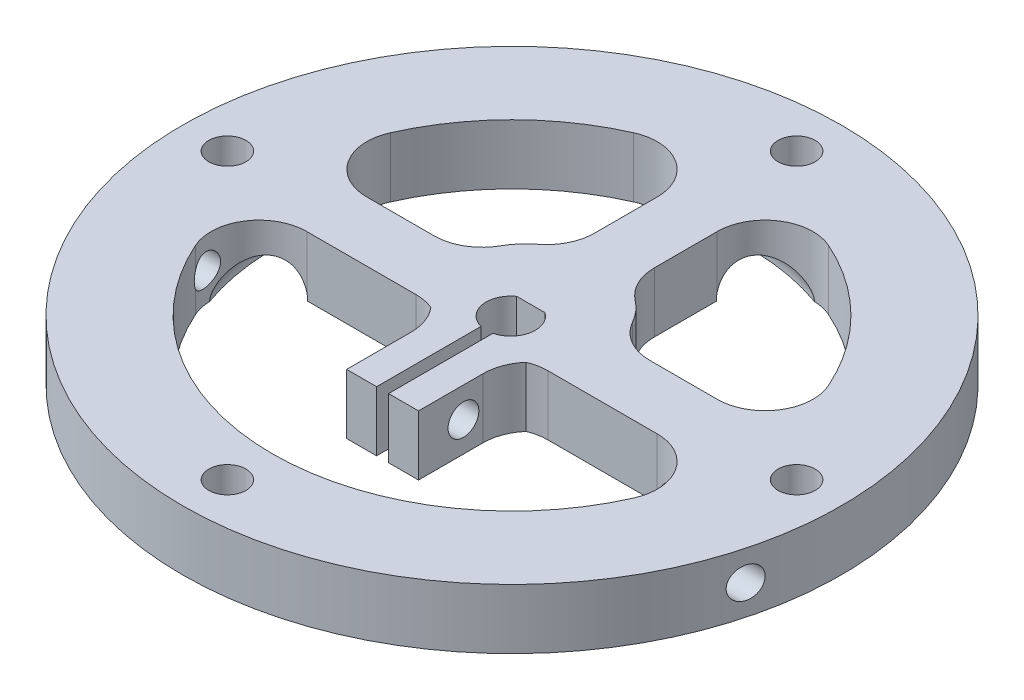
SolidWorks part; units mm, degrees
ref_plane "Front Plane" through (0, 0, 0) normal (0, 0, 1) x (1, 0, 0)
ref_plane "Top Plane" through (0, 0, 0) normal (0, 1, 0) x (1, 0, 0)
ref_plane "Right Plane" through (0, 0, 0) normal (1, 0, 0) x (0, 0, -1)
ref_plane "Plane1" through (0, 46.35, 0) normal (0, 1, 0) x (1, 0, 0)
sketch "Sketch1" plane through (0, 46.35, 0) normal (0, 1, 0) x (1, 0, 0)
  line L0 (-3.81, -4.191) -> (-3.81, -13.716)
  line L3 (-1.5, 2) -> (1.5, 2) construction
  line L4 (-1.5, 2) -> (1.5, 2)
  line L5 (0, -0.127) -> (0, -30.1625) construction
  line L6 (3.81, -8.9535) -> (-3.81, -8.9535) construction
  line L7 (-3.81, -13.716) -> (-0.635, -13.716)
  line L8 (-0.635, -13.716) -> (-0.635, -2.6511)
  line L10 (3.81, -13.716) -> (0.635, -13.716)
  line L11 (0.635, -13.716) -> (0.635, -2.6511)
  line L12 (3.81, -13.716) -> (3.81, -4.191)
  line L13 (0, 0) -> (0, 30.1625) construction
  line L14 (0, 0) -> (-30.1625, 0) construction
  line L15 (0, 0) -> (30.1625, 0) construction
  line L16 (-3.175, 8.9803) -> (-3.175, 25.2008)
  line L17 (3.175, 8.9803) -> (3.175, 25.2008)
  line L18 (-7.8651, 3.175) -> (-25.2008, 3.175)
  line L19 (-5.3988, -3.175) -> (-25.2008, -3.175)
  line L20 (5.3988, -3.175) -> (25.2008, -3.175)
  line L21 (7.8651, 3.175) -> (25.2008, 3.175)
  arc A0 (-3.81, -4.191) -> (-3.175, 8.9803) centre (-0.8007, 2.2649) cw
  arc A3 (-1.5, 2) -> (1.5, 2) centre (0, -0.127) ccw
  arc A4 (-1.5, 2) -> (1.5, 2) centre (0, 0) ccw construction
  arc A5 (-1.5, 2) -> (1.5, 2) centre (0, 0) ccw
  arc A6 (3.81, -4.191) -> (5.3988, -3.175) centre (0.8007, 2.2649) ccw
  arc A7 (3.175, 8.9803) -> (-3.175, 8.9803) centre (0, 0) ccw
  arc A9 (-25.2008, -3.175) -> (25.2008, -3.175) centre (0, 0) ccw
  circle A10 centre (0, 0) radius 30.1625 construction
  circle A11 centre (0, 0) radius 34.925
  circle A12 centre (-30.1625, 0) radius 1.9685
  circle A13 centre (0, 30.1625) radius 1.9685
  circle A14 centre (30.1625, 0) radius 1.9685
  circle A15 centre (0, -30.1625) radius 1.9685
  arc A16 (-3.175, 25.2008) -> (-25.2008, 3.175) centre (0, 0) ccw
  arc A17 (7.8651, 3.175) -> (3.175, 8.9803) centre (0.8007, 2.2649) ccw
  arc A18 (25.2008, 3.175) -> (3.175, 25.2008) centre (0, 0) ccw
  point P49 (0, 0)
  dimension "D4" = 9.525
  dimension "D6" = 6.35
  dimension "D10" = 69.85
  dimension "D11" = 9.525
  dimension "D12" = 4.7625
  dimension "D13" = 3.937
  dimension "D1" = 0.127
  dimension "D2" = 1.27
  dimension "D3" = 9.525
  dimension "D5" = 3.175
  dimension "D7" = 6.35
  dimension "D8" = 6.35
  dimension "D9" = 1.016
  dimension "D14" = 4
extrude "Boss-Extrude1" add sketch "Sketch1" along normal blind 6.35 contours A7 L7 L8 A3 L4 L11 L10 region at (-33.9372, 46.35, 0)
sketch "Sketch2" plane through (-3.81, 0, 0) normal (-1, 0, 0) x (0, 0, 1)
  line L0 (13.716, 52.7) -> (4.191, 46.35) construction
  circle A0 centre (8.9535, 49.525) radius 1.6319
  dimension "D1" = 3.2639
extrude "Cut-Extrude1" cut sketch "Sketch2" against normal through all both and the other way through all
fillet "Fillet1" radius 5.08 14 edges at (25.2008, 49.525, 3.175) (5.3988, 49.525, 3.175) (3.81, 49.525, 4.191) (-3.81, 49.525, 4.191) (-5.3988, 49.525, 3.175) (7.8651, 49.525, -3.175) (25.2008, 49.525, -3.175) (3.175, 49.525, -25.2008) (3.175, 49.525, -8.9803) (-3.175, 49.525, -25.2008) (-25.2008, 49.525, -3.175) (-7.8651, 49.525, -3.175) (-3.175, 49.525, -8.9803) (-25.2008, 49.525, 3.175)
sketch "Sketch3" plane through (0, 0, 0) normal (1, 0, 0) x (0, 0, -1)
  line L1 (11.9262, 46.35) -> (18.5676, 46.35) construction
  line L2 (0, 46.35) -> (21.9202, 46.35) construction
  line L3 (-34.925, 46.35) -> (34.925, 46.35) construction
  line L4 (25.0952, 46.35) -> (18.7452, 46.35)
  arc A0 (25.0952, 46.35) -> (18.7452, 46.35) centre (21.9202, 46.35) ccw
  dimension "D1" = 6.35
  dimension "D2" = 21.9202
ref_axis "Axis1" through (0, 52.7, 0) along (0, -1, 0)
revolve "Cut-Revolve1" cut sketch "Sketch3" angle 360 about axis through (0, 52.7, 0) along (0, -1, 0)
